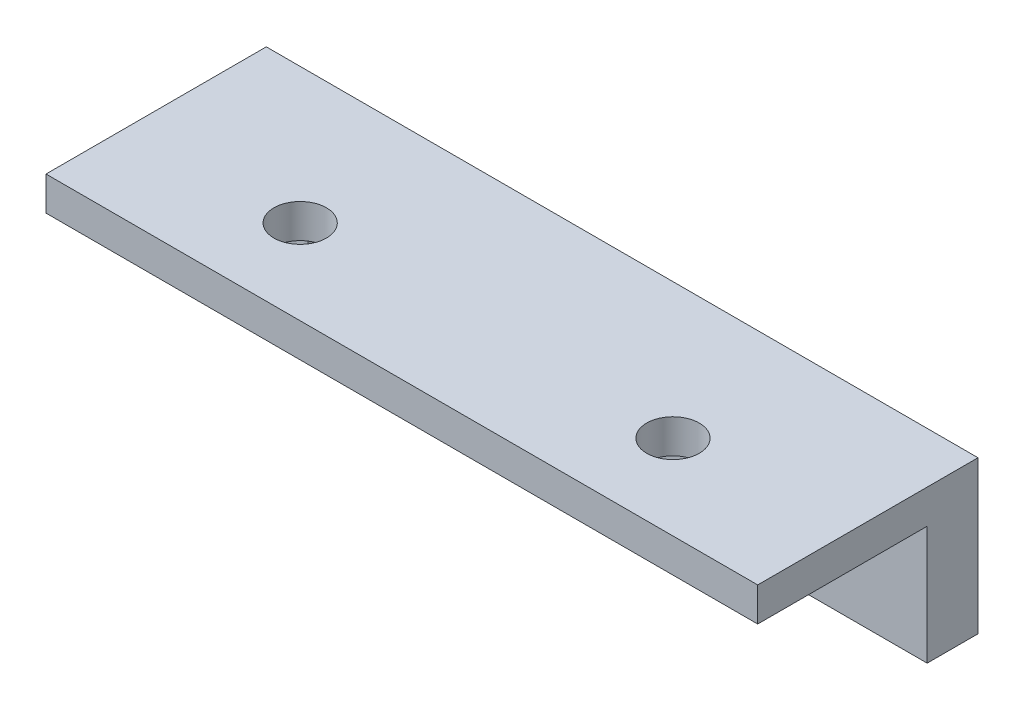
SolidWorks part; units mm, degrees
ref_plane "前视基准面" through (0, 0, 0) normal (0, 0, 1) x (1, 0, 0)
ref_plane "上视基准面" through (0, 0, 0) normal (0, 1, 0) x (1, 0, 0)
ref_plane "右视基准面" through (0, 0, 0) normal (1, 0, 0) x (0, 0, -1)
sketch "草图1" plane through (0, 0, 0) normal (0, 0, 1) x (1, 0, 0)
  line L7 (5, 14) -> (47, 14)
  line L9 (5, 14) -> (47, 14)
  line L11 (5, 5) -> (47, 5)
  line L13 (5, 12) -> (47, 12)
  line L15 (5, 5) -> (5, 14)
  line L17 (47, 5) -> (47, 14)
  circle A0 centre (40, 8.4) radius 1.55
  circle A1 centre (12, 8.4) radius 1.55
  point P10 (26, 8.4)
extrude "凸台-拉伸5" add sketch "草图1" along normal blind 3 contours L11 L17 L13 L15 A1 A0 region at (26, 8.5054, 0)
extrude "凸台-拉伸6" add sketch "草图1<6>" along normal blind 13 contours L13 L17 L7 L15 region at (26, 13, 0)
sketch "草图1<6>" plane through (0, 0, 0) normal (0, 0, 1) x (1, 0, 0) same geometry as "草图1"
sketch "草图3" plane through (5, 0, 0) normal (-1, 0, 0) x (0, 0, 1)
  line L0 (3, 12) -> (3, 14)
  line L1 (13, 14) -> (0, 14) construction
sketch "草图4" plane through (0, 14, 0) normal (0, 1, 0) x (1, 0, 0)
  line L0 (5, -3) -> (47, -3) construction
  line L1 (47, -13) -> (47, 0) construction
  line L2 (5, -13) -> (15, -13)
  line L3 (5, -13) -> (47, -13) construction
  line L4 (15, -13) -> (15, -3)
  line L5 (47, -13) -> (37, -13)
  line L6 (37, -13) -> (37, -3)
  circle A0 centre (15, -8) radius 1.55
  circle A1 centre (37, -8) radius 1.55
extrude "切除-拉伸1" cut sketch "草图4" against normal blind 13 contours L4 A0 | L4 A0 | L6 A1 | L6 A1 region at (14.3422, 14, 8) region at (15.6578, 14, 8) region at (36.3422, 14, 8) region at (37.6578, 14, 8)
